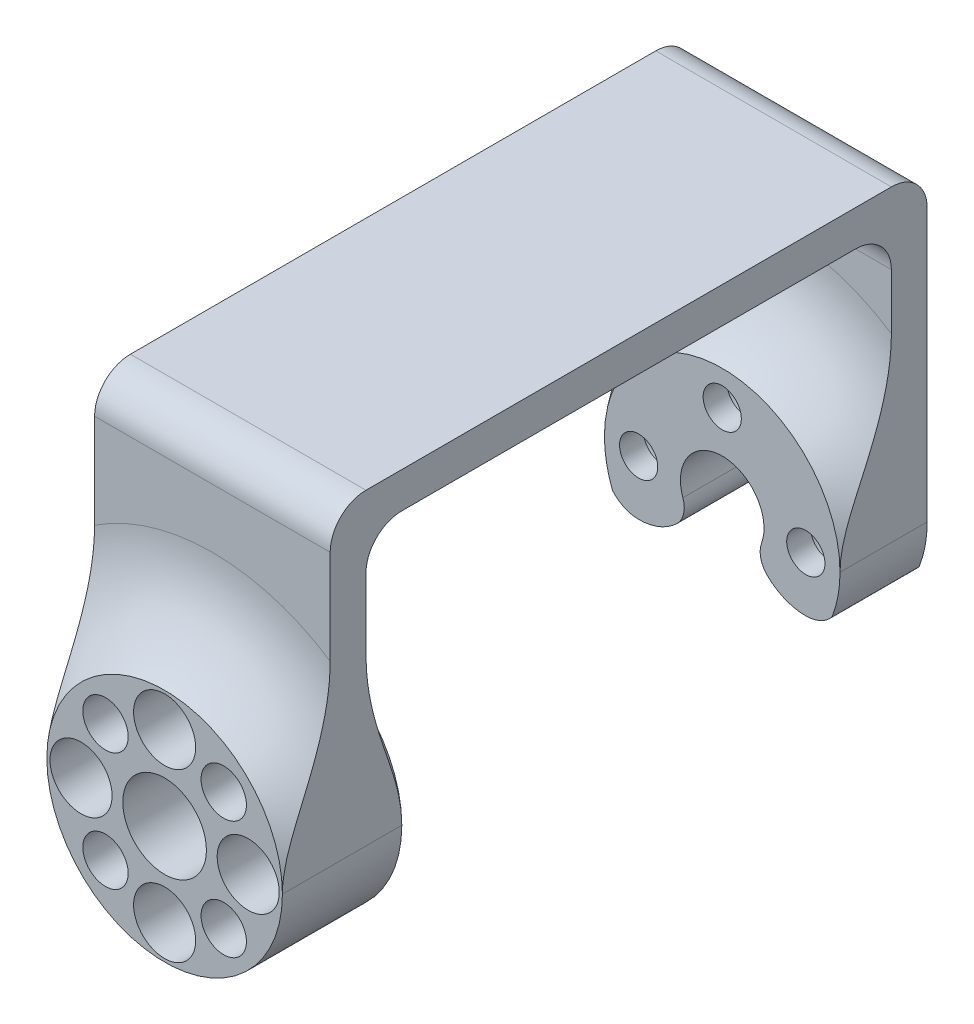
SolidWorks part; units mm, degrees
note: The reader was unsure of these and kept them because the rebuilt part matched: shared geometry of "Sketch4<3>", "Sketch5<4>".
material "PLA"
ref_plane "Front Plane" through (0, 0, 0) normal (1, 0, 0) x (0, 1, 0)
ref_plane "Top Plane" through (0, 0, 0) normal (0, 0, 1) x (0, 1, 0)
ref_plane "Right Plane" through (0, 0, 0) normal (0, 1, 0) x (-1, 0, 0)
sketch "Sketch2" plane through (0, 0, 0) normal (0, 0, 1) x (0, 1, 0)
  line L1 (-201.4286, 287.5871) -> (-181.4286, 287.5871)
  line L2 (-201.4286, 287.5871) -> (-201.4286, 267.8571)
  line L3 (-201.4286, 267.8571) -> (-181.4286, 267.8571)
  line L4 (-181.4286, 287.5871) -> (-181.4286, 267.8571)
  line L5 (-181.4286, 287.5871) -> (-165.4286, 287.5871)
  line L6 (-181.4286, 287.5871) -> (-181.4286, 267.8571)
  line L7 (-181.4286, 267.8571) -> (-165.4286, 267.8571)
  line L8 (-165.4286, 287.5871) -> (-165.4286, 267.8571)
  dimension "D1" = 19.73
  dimension "D2" = 20
  dimension "D3" = 16
extrude "Boss-Extrude1" add sketch "Sketch2" along normal blind 50 contours L8 L5 L4 L7
sketch "Sketch3" plane through (0, -201.4286, 0) normal (0, -1, 0) x (1, 0, 0)
  line L0 (-287.5871, 50) -> (-287.5871, 0) construction
  line L1 (-287.5871, 47) -> (-267.8571, 47)
  line L2 (-287.5871, 47) -> (-287.5871, 3)
  line L3 (-287.5871, 3) -> (-267.8571, 3)
  line L4 (-267.8571, 47) -> (-267.8571, 3)
  line L5 (-267.8571, 50) -> (-267.8571, 0) construction
  line L6 (-287.5871, 0) -> (-267.8571, 0) construction
  line L7 (-287.5871, 50) -> (-267.8571, 50) construction
  dimension "D1" = 3
  dimension "D2" = 3
extrude "Cut-Extrude1" cut sketch "Sketch3" against normal offset from surface (33 mm away) 3 up to face at (-277.7221, -165.4286, 25)
fillet "Fillet1" radius 3 4 edges at (-277.7221, -165.4286, 50) (-277.7221, -165.4286, 0) (-277.7221, -168.4286, 47) (-277.7221, -168.4286, 3)
sketch "Sketch4" plane through (0, 0, 0) normal (0, 0, -1) x (1, 0, 0)
  line L0 (-277.7221, 165.4286) -> (-277.7221, 201.4286) construction
  line L1 (-267.8571, 165.4286) -> (-287.5871, 165.4286) construction
  line L2 (-287.5871, 201.4286) -> (-267.8571, 201.4286) construction
  line L3 (-284.7225, 191.2286) -> (-277.7221, 198.2289) construction
  line L4 (-277.7221, 198.2289) -> (-270.7218, 191.2286) construction
  line L5 (-270.7218, 191.2286) -> (-277.7221, 184.2282) construction
  line L6 (-277.7221, 184.2282) -> (-284.7225, 191.2286) construction
  line L7 (-287.5871, 195.8286) -> (-284.7225, 195.8286)
  line L8 (-287.5871, 201.4286) -> (-287.5871, 168.4286) construction
  line L9 (-267.8571, 195.8286) -> (-270.7218, 195.8286)
  line L10 (-267.8571, 201.4286) -> (-267.8571, 168.4286) construction
  circle A0 centre (-277.7221, 191.2286) radius 7.0004
  circle A1 centre (-277.7221, 198.2289) radius 1.6
  circle A2 centre (-270.7218, 191.2286) radius 1.6
  circle A3 centre (-284.7225, 191.2286) radius 1.6
  circle A8 centre (-277.7221, 184.2282) radius 1.6
  arc A9 (-284.7225, 195.8286) -> (-280.5859, 189.2164) centre (-284.7225, 191.2286) cw
  arc A10 (-280.5859, 189.2164) -> (-274.8584, 189.2164) centre (-277.7221, 191.2286) ccw
  circle A11 centre (-277.7221, 191.2286) radius 3.5
  arc A12 (-270.7218, 195.8286) -> (-274.8584, 189.2164) centre (-270.7218, 191.2286) ccw
  circle A13 centre (-277.7221, 191.2286) radius 9.865
  point P29 (-275.2718, 191.2286)
  point P30 (-280.6421, 189.2988)
  line M1 (-287.5871, 201.4286) -> (-287.5871, 168.4286)
  line M3 (-267.8571, 168.4286) -> (-267.8571, 201.4286)
  line M4 (-267.8571, 201.4286) -> (-287.5871, 201.4286)
  dimension "D1" = 10.2
  dimension "D2" = 3.2
  dimension "D4" = 7
  dimension "D5" = 3
  dimension "D3" = 9.9
extrude "Cut-Extrude2" cut sketch "Sketch4" against normal up to next contours A12 A0 A1 A9 A10 A11 | A11 | L9 A13 L7 A9 A0 A1 A12 | A13 L9 L7 M3 M4 M1 | A11 A12 | A9 A11 | A3 | A2 | A8
fillet "Fillet2" radius 2.85 2 edges at (-267.8571, -195.8286, 1.5) (-287.5871, -195.8286, 1.5)
extrude "Cut-Extrude3" cut sketch "Sketch4<3>" against normal through all from surface at -47 contours A11 | A0 A1 | A0 A1 | A0 A3 | A0 A3 | A0 A8 | A0 A8 | A0 A2 | A0 A2 | A9 A11 | A11 A12 | A13
sketch "Sketch4<3>" plane through (0, 0, 0) normal (0, 0, -1) x (1, 0, 0) same geometry as "Sketch4"
sketch "Sketch5" plane through (0, 0, 50) normal (0, 0, 1) x (1, 0, 0)
  line L0 (-282.6721, -186.2786) -> (-272.7721, -186.2786) construction
  line L1 (-272.7721, -186.2786) -> (-272.7721, -196.1786) construction
  line L2 (-272.7721, -196.1786) -> (-282.6721, -196.1786) construction
  line L3 (-282.6721, -186.2786) -> (-282.6721, -196.1786) construction
  line L4 (-282.6721, -186.2786) -> (-272.7721, -196.1786) construction
  line L5 (-282.6721, -196.1786) -> (-272.7721, -186.2786) construction
  line L6 (-287.5871, -201.4286) -> (-287.5871, -168.4286) construction
  circle A1 centre (-277.7221, -191.2286) radius 3.5 construction
  circle A2 centre (-277.7221, -191.2286) radius 9.865
  circle A3 centre (-270.7218, -191.2286) radius 1.6 construction
  circle A4 centre (-277.7221, -184.2282) radius 1.6 construction
  circle A5 centre (-284.7225, -191.2286) radius 1.6 construction
  circle A6 centre (-270.7218, -191.2286) radius 1.6
  circle A7 centre (-277.7221, -184.2282) radius 1.6
  circle A8 centre (-284.7225, -191.2286) radius 1.6
  circle A9 centre (-284.7225, -191.2286) radius 2.6
  circle A10 centre (-277.7221, -184.2282) radius 2.6
  circle A11 centre (-270.7218, -191.2286) radius 2.6
  circle A12 centre (-282.6721, -186.2786) radius 1.9
  circle A13 centre (-272.7721, -186.2786) radius 1.9
  circle A14 centre (-272.7721, -196.1786) radius 1.9
  circle A15 centre (-282.6721, -196.1786) radius 1.9
  circle A17 centre (-277.7221, -191.2286) radius 3.5
  circle A18 centre (-277.7221, -198.2289) radius 1.6 construction
  circle A19 centre (-277.7221, -198.2289) radius 1.6
  circle A20 centre (-277.7221, -198.2289) radius 2.6
  circle M41 centre (-284.7225, -191.2286) radius 1.6
  circle M42 centre (-277.7221, -198.2289) radius 1.6
  circle M43 centre (-270.7218, -191.2286) radius 1.6
  circle M44 centre (-277.7221, -184.2282) radius 1.6
  circle M45 centre (-277.7221, -191.2286) radius 3.5
  dimension "D1" = 1
  dimension "D2" = 3.8
  dimension "D3" = 9.9
  dimension "D4" = 1
extrude "Boss-Extrude3" add sketch "Sketch5" along normal blind 4 contours A2 A20 A15 A14 A13 A12 A11 A10 A9 M45
sketch "Sketch6" plane through (0, 0, 54) normal (0, 0, 1) x (1, 0, 0)
  line L0 (-287.5871, -168.4286) -> (-287.5871, -191.2286) construction
  line L1 (-267.8571, -191.2286) -> (-267.8571, -168.4286) construction
  line L2 (-267.8571, -168.4286) -> (-287.5871, -168.4286) construction
  line L3 (-267.8571, -201.4286) -> (-267.8571, -191.2286) construction
  line L4 (-287.5871, -191.2286) -> (-287.5871, -201.4286) construction
  line L5 (-287.5871, -201.4286) -> (-267.8571, -201.4286) construction
  line L6 (-287.5871, -168.4286) -> (-287.5871, -191.2286)
  line L7 (-267.8571, -191.2286) -> (-267.8571, -168.4286)
  line L8 (-267.8571, -168.4286) -> (-287.5871, -168.4286)
  line L9 (-267.8571, -201.4286) -> (-267.8571, -191.2286)
  line L10 (-287.5871, -191.2286) -> (-287.5871, -201.4286)
  line L11 (-287.5871, -201.4286) -> (-267.8571, -201.4286)
  arc A0 (-267.8571, -191.2286) -> (-287.5871, -191.2286) centre (-277.7221, -191.2286) ccw construction
  circle A1 centre (-277.7221, -191.2286) radius 9.865
  circle A2 centre (-277.7221, -191.2286) radius 9.865
  arc A3 (-287.5871, -191.2286) -> (-267.8571, -191.2286) centre (-277.7221, -191.2286) ccw construction
  arc A4 (-267.8571, -191.2286) -> (-287.5871, -191.2286) centre (-277.7221, -191.2286) ccw
  arc A5 (-287.5871, -191.2286) -> (-267.8571, -191.2286) centre (-277.7221, -191.2286) ccw
  circle M11 centre (-277.7221, -191.2286) radius 9.865
  dimension "D1" = 0
extrude "Cut-Extrude4" cut sketch "Sketch6" against normal through all contours L10 L11 L9 M11
sketch "Sketch7" plane through (0, 0, 47) normal (0, 0, -1) x (1, 0, 0)
  circle A0 centre (-270.7218, 191.2286) radius 1.6 construction
  circle A1 centre (-277.7221, 198.2289) radius 1.6
  circle A2 centre (-277.7221, 198.2289) radius 1.6
  circle A3 centre (-277.7221, 184.2282) radius 1.6 construction
  circle A4 centre (-284.7225, 191.2286) radius 1.6 construction
  circle A5 centre (-270.7218, 191.2286) radius 1.6
  circle A6 centre (-277.7221, 184.2282) radius 1.6
  circle A7 centre (-284.7225, 191.2286) radius 1.6
  circle A8 centre (-277.7221, 191.2286) radius 3.5
  circle A9 centre (-277.7221, 191.2286) radius 9.865
  arc A10 (-267.8571, 191.2286) -> (-287.5871, 191.2286) centre (-277.7221, 191.2286) ccw construction
  dimension "D1" = 0
extrude "Boss-Extrude4" add sketch "Sketch7" along normal blind 3
sketch "Sketch8" plane through (0, 0, 3) normal (0, 0, 1) x (1, 0, 0)
  line L0 (-287.5871, -171.4286) -> (-287.5871, -191.2286) construction
  line L1 (-267.8571, -171.4286) -> (-267.8571, -191.2286) construction
  line L2 (-287.5871, -171.4286) -> (-287.5871, -191.2286)
  line L3 (-267.8571, -171.4286) -> (-267.8571, -191.2286)
  arc A0 (-284.7225, -195.8286) -> (-280.5859, -193.2407) centre (-284.7225, -191.2286) ccw construction
  arc A1 (-286.9083, -194.8248) -> (-284.7371, -195.8286) centre (-284.7371, -192.9786) ccw construction
  arc A2 (-287.5871, -191.2286) -> (-286.9083, -194.8248) centre (-277.7221, -191.2286) ccw construction
  arc A3 (-268.536, -194.8248) -> (-267.8571, -191.2286) centre (-277.7221, -191.2286) ccw construction
  arc A4 (-270.7071, -195.8286) -> (-268.536, -194.8248) centre (-270.7071, -192.9786) ccw construction
  arc A5 (-274.8584, -193.2407) -> (-270.7218, -195.8286) centre (-270.7218, -191.2286) ccw construction
  arc A6 (-284.7225, -195.8286) -> (-280.5859, -193.2407) centre (-284.7225, -191.2286) ccw
  arc A7 (-286.9083, -194.8248) -> (-284.7371, -195.8286) centre (-284.7371, -192.9786) ccw
  arc A8 (-287.5871, -191.2286) -> (-286.9083, -194.8248) centre (-277.7221, -191.2286) ccw
  arc A9 (-268.536, -194.8248) -> (-267.8571, -191.2286) centre (-277.7221, -191.2286) ccw
  arc A10 (-270.7071, -195.8286) -> (-268.536, -194.8248) centre (-270.7071, -192.9786) ccw
  arc A11 (-274.8584, -193.2407) -> (-270.7218, -195.8286) centre (-270.7218, -191.2286) ccw
  arc A12 (-274.8584, -193.2407) -> (-280.5859, -193.2407) centre (-277.7221, -191.2286) ccw construction
  circle A13 centre (-284.7225, -191.2286) radius 1.6
  circle A14 centre (-284.7225, -191.2286) radius 1.6
  circle A15 centre (-277.7221, -184.2282) radius 1.6
  circle A16 centre (-277.7221, -184.2282) radius 1.6
  circle A17 centre (-270.7218, -191.2286) radius 1.6
  circle A18 centre (-270.7218, -191.2286) radius 1.6
  arc A19 (-274.8584, -193.2407) -> (-280.5859, -193.2407) centre (-277.7221, -191.2286) ccw
  circle A20 centre (-277.7221, -191.2286) radius 9.865
  circle A21 centre (-277.7221, -191.2286) radius 9.865 construction
  circle M5 centre (-277.7221, -184.2282) radius 1.6
  circle M6 centre (-270.7218, -191.2286) radius 1.6
  circle M7 centre (-284.7225, -191.2286) radius 1.6
  arc M8 (-268.536, -194.8248) -> (-267.8571, -191.2286) centre (-277.7221, -191.2286) ccw
  arc M12 (-287.5871, -191.2286) -> (-286.9083, -194.8248) centre (-277.7221, -191.2286) ccw
  arc M13 (-286.9083, -194.8248) -> (-284.7371, -195.8286) centre (-284.7371, -192.9786) ccw
  line M14 (-284.7371, -195.8286) -> (-284.7225, -195.8286)
  arc M15 (-284.7225, -195.8286) -> (-280.5859, -193.2407) centre (-284.7225, -191.2286) ccw
  arc M16 (-280.5859, -193.2407) -> (-274.8584, -193.2407) centre (-277.7221, -191.2286) cw
  arc M17 (-274.8584, -193.2407) -> (-270.7218, -195.8286) centre (-270.7218, -191.2286) ccw
  line M18 (-270.7218, -195.8286) -> (-270.7071, -195.8286)
  arc M19 (-270.7071, -195.8286) -> (-268.536, -194.8248) centre (-270.7071, -192.9786) ccw
  dimension "D1" = 0
  dimension "D2" = 0
  dimension "D3" = 0
extrude "Boss-Extrude5" add sketch "Sketch8" along normal blind 4.3 contours A20 M8 M12 M13 M14 M15 M16 M17 M18 M19 M6 M7 M5
sketch "Sketch9" plane through (0, 0, 0) normal (0, 0, -1) x (1, 0, 0)
  circle A13 centre (-284.7225, 191.2286) radius 2.6
  circle A14 centre (-284.7225, 191.2286) radius 2.6
  circle A16 centre (-277.7221, 184.2282) radius 2.6
  circle A17 centre (-277.7221, 184.2282) radius 2.6
  circle A19 centre (-270.7218, 191.2286) radius 2.6
  circle A20 centre (-270.7218, 191.2286) radius 2.6
  dimension "D1" = 1
  dimension "D2" = 1
  dimension "D3" = 1
extrude "Cut-Extrude5" cut sketch "Sketch9" against normal offset from surface (5.3 mm away) 2 up to face at (-269.1218, -191.2286, 7.3)
extrude "Cut-Extrude6" cut sketch "Sketch5<4>" against normal offset from surface (4 mm away) 2 contours A20 M42 | A11 M43 | A10 M44 | A9 M41 up to face at (-286.3225, -191.2286, 44)
sketch "Sketch5<4>" plane through (0, 0, 50) normal (0, 0, 1) x (1, 0, 0) same geometry as "Sketch5"
fillet "Fillet3" radius 10 3 edges at (-277.7221, -181.3636, 50) (-277.7221, -181.3636, 47) (-277.7221, -181.3636, 3)
fillet "Fillet4" radius 2 2 edges at (-280.5859, -193.2407, 3.65) (-274.8584, -193.2407, 3.65)
sketch "Sketch11" plane through (0, 0, 54) normal (0, 0, 1) x (1, 0, 0)
  circle A0 centre (-272.7721, -196.1786) radius 1.9 construction
  circle A1 centre (-282.6721, -196.1786) radius 1.9 construction
  circle A2 centre (-272.7721, -186.2786) radius 1.9 construction
  circle A3 centre (-282.6721, -186.2786) radius 1.9 construction
  circle A4 centre (-272.7721, -196.1786) radius 1.9
  circle A5 centre (-282.6721, -196.1786) radius 1.9
  circle A6 centre (-272.7721, -186.2786) radius 1.9
  circle A7 centre (-282.6721, -186.2786) radius 1.9
extrude "Cut-Extrude7" cut sketch "Sketch11" against normal blind 6
